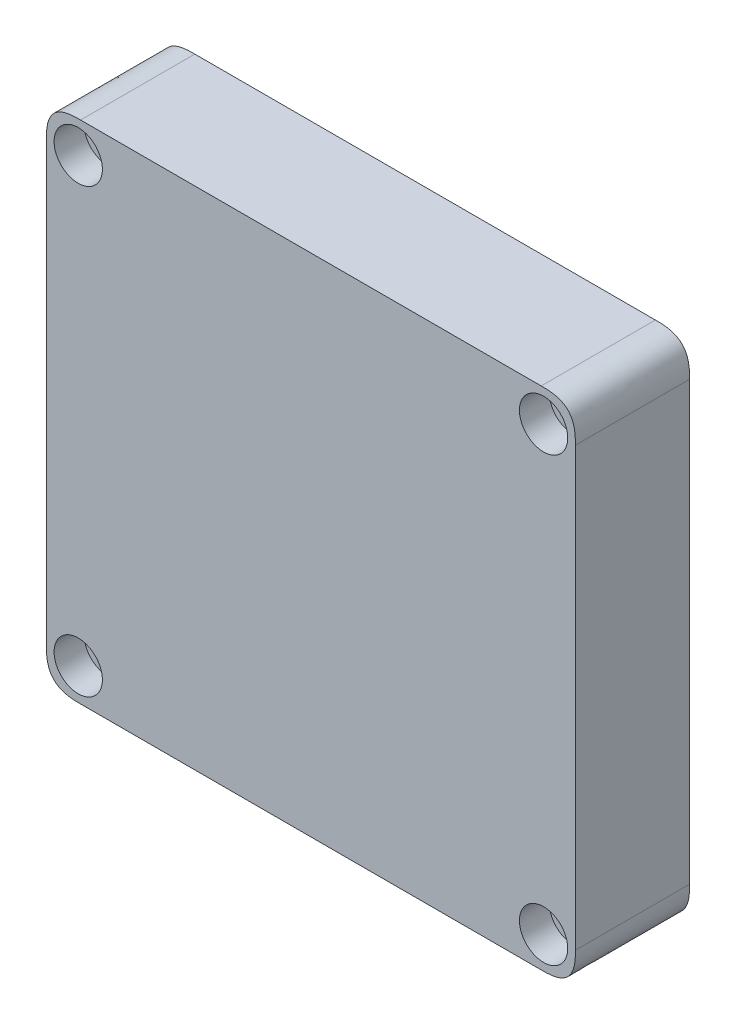
SolidWorks part; units mm, degrees
ref_plane "Front Plane" through (0, 0, 0) normal (0, 0, 1) x (1, 0, 0)
ref_plane "Top Plane" through (0, 0, 0) normal (0, 1, 0) x (1, 0, 0)
ref_plane "Right Plane" through (0, 0, 0) normal (1, 0, 0) x (0, 0, -1)
sketch "Sketch1" plane through (0, 0, 0) normal (0, 0, 1) x (1, 0, 0)
  arc A15 (50.4872, 1.1347) -> (50.4872, -1.1347) centre (48.75, 0) ccw
  arc A16 (24.2609, 44.2906) -> (26.2263, 43.1559) centre (24.375, 42.2187) ccw
  arc A17 (-26.2263, 43.1559) -> (-24.2609, 44.2906) centre (-24.375, 42.2187) ccw
  arc A18 (-50.4872, -1.1347) -> (-50.4872, 1.1347) centre (-48.75, 0) ccw
  arc A19 (-24.2609, -44.2906) -> (-26.2263, -43.1559) centre (-24.375, -42.2187) ccw
  arc A20 (26.2263, -43.1559) -> (24.2609, -44.2906) centre (24.375, -42.2187) ccw
  circle A21 centre (0, 0) radius 9.75
  circle A22 centre (-20, 15) radius 2
  circle A23 centre (20, 15) radius 2
  circle A24 centre (20, -23) radius 2
  circle A25 centre (-20, -23) radius 2
  circle A26 centre (-27.2, -31.28) radius 2.075
  circle A27 centre (27.2, -31.28) radius 2.075
  circle A28 centre (27.2, 20.4) radius 2.075
  circle A29 centre (-27.2, 20.4) radius 2.075
sketch "Sketch3" plane through (0, 0, 0) normal (0, 0, 1) x (1, 0, 0)
  line L3 (16, -35) -> (16, -19)
  line L4 (-16, -19) -> (-16, -35)
  line L5 (-16, -35) -> (16, -35)
  line L16 (16, -19) -> (16, -29)
  line L17 (17.0471, -27.4916) -> (20.8734, -26.0636)
  line L18 (23, -23) -> (23, 15)
  line L19 (20, 18) -> (-20, 18)
  line L20 (-23, 15) -> (-23, -23)
  line L21 (-20.8734, -26.0636) -> (-17.0471, -27.4916)
  line L22 (-16, -29) -> (-16, -19)
  line L23 (-16, -19) -> (16, -19)
  arc A12 (17.0471, -27.4916) -> (16, -29) centre (17.61, -29) ccw
  arc A13 (20.8734, -26.0636) -> (23, -23) centre (19.73, -23) ccw
  arc A14 (23, 15) -> (20, 18) centre (20, 15) ccw
  arc A15 (-20, 18) -> (-23, 15) centre (-20, 15) ccw
  arc A16 (-23, -23) -> (-20.8734, -26.0636) centre (-19.73, -23) ccw
  arc A17 (-16, -29) -> (-17.0471, -27.4916) centre (-17.61, -29) ccw
sketch "Sketch2" plane through (0, 0, 0) normal (0, 0, 1) x (1, 0, 0)
  line L0 (-16, -35) -> (16, -35) construction
  line L1 (-16, -35) -> (16, -35)
  line L3 (-30.92, -35) -> (30.92, -35)
  line L4 (-30.92, -35) -> (-30.92, 24.12)
  line L5 (-30.92, 24.12) -> (30.92, 24.12)
  line L6 (30.92, -35) -> (30.92, 24.12)
  line L7 (-30.92, -35) -> (30.92, 24.12) construction
  line L8 (-30.92, 24.12) -> (30.92, -35) construction
  line L9 (-23.9, -35) -> (23.9, -35)
  line L10 (-23.9, -35) -> (-23.9, 18.9)
  line L11 (-23.9, 18.9) -> (23.9, 18.9)
  line L12 (23.9, -35) -> (23.9, 18.9)
  line L13 (-23.9, -35) -> (23.9, 18.9) construction
  line L14 (-23.9, 18.9) -> (23.9, -35) construction
  circle A0 centre (-27.2, 20.4) radius 1.5
  circle A1 centre (27.2, 20.4) radius 1.5
  circle A2 centre (27.2, -31.28) radius 1.5
  circle A3 centre (-27.2, -31.28) radius 1.5
  point P0 (-27.2, -31.28)
  point P2 (27.2, -31.28)
  point P4 (27.2, 20.4)
  point P6 (-27.2, 20.4)
  point P19 (0, -5.44)
  point P25 (0, -8.05)
  dimension "D1" = 3
  dimension "D2" = 3
  dimension "D3" = 3
  dimension "D4" = 3
  dimension "D5" = 3.72
  dimension "D6" = 3.72
  dimension "D7" = 3.72
  dimension "D8" = 3.9
  dimension "D9" = 3.9
  dimension "D10" = 3.9
extrude "Boss-Extrude1" add sketch "Sketch2" along normal blind 10.35 contours L12 L3 L6 L5 L4 L10 L11 A3 A2 A1 A0 region at (-27.41, -34.1445, 0)
extrude "Boss-Extrude2" add sketch "Sketch2<3>" along normal blind 3 from surface contours L12 L3 L6 L5 L4 L10 L11 A3 A2 A1 A0 | L3 L12 L11 L10 L1 region at (0, -8.05, 0) region at (-27.41, -34.1445, 0) starting at face at (-25.7, -31.28, 10.35)
sketch "Sketch2<3>" plane through (0, 0, 0) normal (0, 0, 1) x (1, 0, 0) same geometry as "Sketch2"
sketch "Sketch6" plane through (0, 0, 0) normal (0, 0, -1) x (-1, 0, 0)
  circle A0 centre (-27.2, 20.4) radius 3
  dimension "D1" = 6
fillet "Fillet1" radius 4 2 edges at (-23.9, 18.9, 5.175) (23.9, 18.9, 5.175) curvature continuous yes
fillet "Fillet2" radius 4 6 edges at (23.9, -35, 5.175) (-23.9, -35, 5.175) (-30.92, -35, 6.675) (30.92, -35, 6.675) (30.92, 24.12, 6.675) (-30.92, 24.12, 6.675) curvature continuous yes
sketch "Sketch7" plane through (0, 0, 13.35) normal (0, 0, 1) x (1, 0, 0)
  circle A0 centre (-27.2, 20.4) radius 2.825
  circle A1 centre (27.2, 20.4) radius 2.825
  circle A2 centre (27.2, -31.28) radius 2.825
  circle A3 centre (-27.2, -31.28) radius 2.825
  point P0 (-27.2, -31.28)
  point P2 (27.2, -31.28)
  point P4 (27.2, 20.4)
  point P6 (-27.2, 20.4)
  dimension "D1" = 5.65
  dimension "D2" = 5.65
  dimension "D3" = 5.65
  dimension "D4" = 5.65
extrude "Cut-Extrude1" cut sketch "Sketch7" against normal blind 3.5
